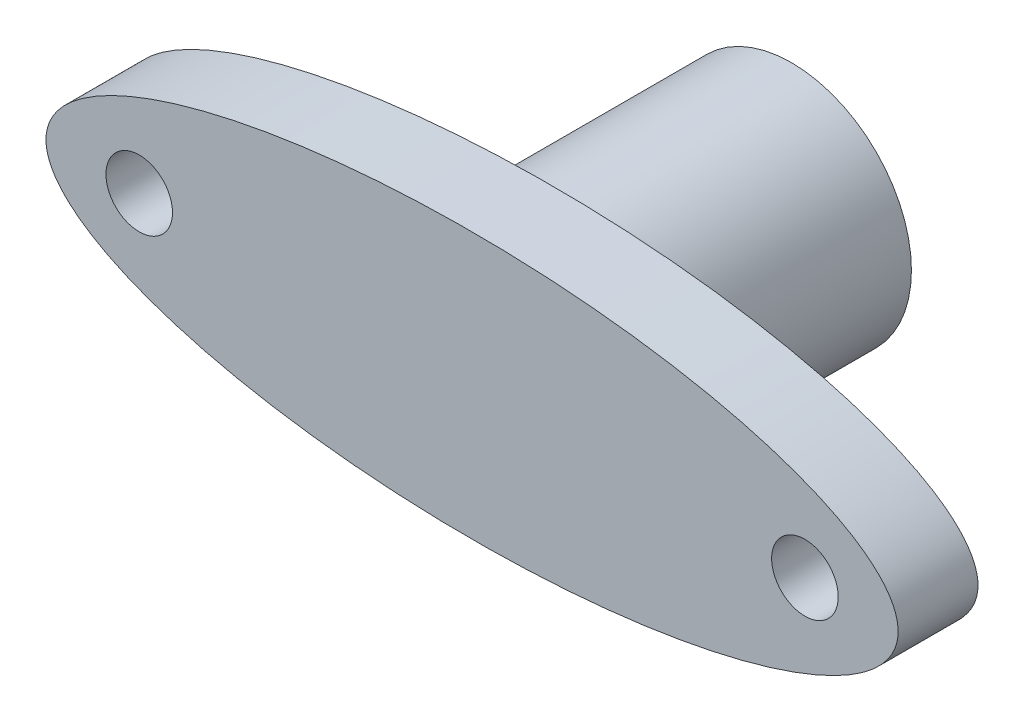
SolidWorks part; units mm, degrees
ref_plane "Alzado" through (0, 0, 0) normal (0, 0, 1) x (1, 0, 0)
ref_plane "Planta" through (0, 0, 0) normal (0, 1, 0) x (1, 0, 0)
ref_plane "Vista lateral" through (0, 0, 0) normal (1, 0, 0) x (0, 0, -1)
sketch "Croquis1" plane through (0, 0, 0) normal (0, 0, 1) x (1, 0, 0)
  line L1 (0.1443, 0) -> (0.0722, 0.125)
  line L2 (0.0722, 0.125) -> (-0.0722, 0.125)
  line L3 (-0.0722, 0.125) -> (-0.1443, 0)
  line L4 (-0.1443, 0) -> (-0.0722, -0.125)
  line L5 (-0.0722, -0.125) -> (0.0722, -0.125)
  line L6 (0.0722, -0.125) -> (0.1443, 0)
  circle A0 centre (0, 0) radius 0.125 construction
  circle A1 centre (0, 0) radius 0.225
  circle A2 centre (0.625, 0) radius 0.0625
  circle A3 centre (-0.625, 0) radius 0.0625
  ellipse E0 centre (0, 0) end of major axis (-0.8, 0) minor radius 0.25
  dimension "D4" = 0.45
  dimension "D5" = 0.125
  dimension "D6" = 0.125
  dimension "D1" = 1.6
  dimension "D2" = 0.5
  dimension "D3" = 0.25
  dimension "D7" = 0.175
  dimension "D8" = 0.175
extrude "Saliente-Extruir1" add sketch "Croquis1" along normal blind 0.15 contours E0 A1 A2 A3 | L5 L6 L1 L2 L3 L4 region at (0, 0, 0) region at (0.7828, 0.007, 0)
extrude "Saliente-Extruir2" add sketch "Croquis1<5>" against normal blind 0.45 separate body contours A1 L6 L5 L4 L3 L2 L1 region at (-0.2186, 0, 0)
sketch "Croquis1<5>" plane through (0, 0, 0) normal (0, 0, 1) x (1, 0, 0) same geometry as "Croquis1"
extrude "Saliente-Extruir3" add sketch "Croquis1<6>" along normal blind 0.15 contours A1 L6 L5 L4 L3 L2 L1 region at (-0.2186, 0, 0)
sketch "Croquis1<6>" plane through (0, 0, 0) normal (0, 0, 1) x (1, 0, 0) same geometry as "Croquis1"
extrude "Saliente-Extruir5" add sketch "Croquis1<8>" against normal blind 0.15 contours L5 L6 L1 L2 L3 L4 | A1 L6 L5 L4 L3 L2 L1 region at (0, 0, 0) region at (-0.2186, 0, 0)
sketch "Croquis1<8>" plane through (0, 0, 0) normal (0, 0, 1) x (1, 0, 0) same geometry as "Croquis1"
sketch "Croquis2" plane through (0, 0, 0) normal (0, 0, 1) x (1, 0, 0)
